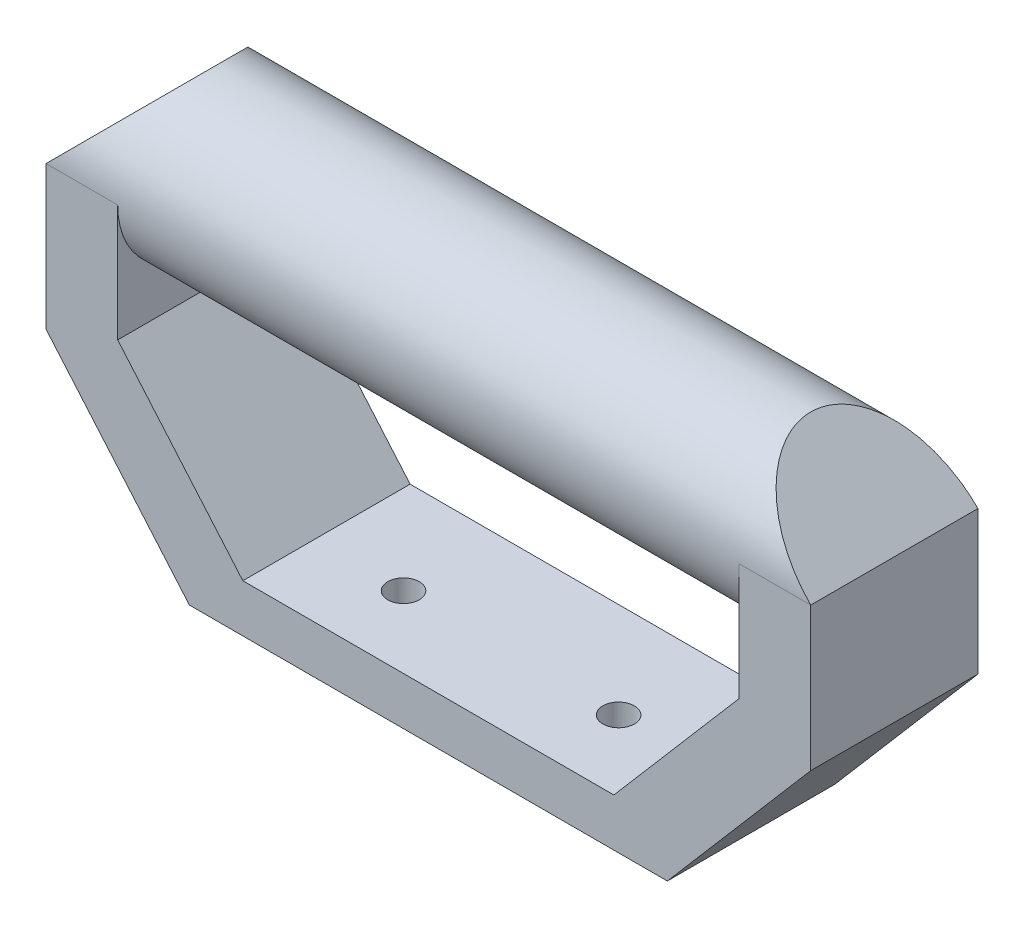
SolidWorks part; units mm, degrees
ref_plane "Front Plane" through (0, 0, 0) normal (0, 0, 1) x (1, 0, 0)
ref_plane "Top Plane" through (0, 0, 0) normal (0, 1, 0) x (1, 0, 0)
ref_plane "Right Plane" through (0, 0, 0) normal (1, 0, 0) x (0, 0, -1)
sketch "Sketch1" plane through (0, 0, 0) normal (0, 1, 0) x (1, 0, 0)
  line L1 (0, 0) -> (100, 0)
  line L2 (0, 0) -> (0, 35)
  line L3 (0, 35) -> (100, 35)
  line L4 (100, 0) -> (100, 35)
  dimension "D1" = 35
  dimension "D2" = 100
extrude "Boss-Extrude1" add sketch "Sketch1" along normal blind 10
sketch "Sketch2" plane through (0, 0, 0) normal (0, 0, 1) x (1, 0, 0)
  line L0 (0, 0) -> (-30, 35)
  line L1 (-30, 35) -> (-30, 65)
  line L2 (0, 0) -> (100, 0) construction
  line L3 (0, 10) -> (100, 10) construction
  line L4 (-30, 65) -> (-15, 65)
  line L5 (-15, 65) -> (-15, 40.5489)
  line L6 (-15, 40.5489) -> (11.1847, 10)
  line L7 (11.1847, 10) -> (0, 0)
  line L8 (50, 0) -> (50, 87.5) construction
  line L9 (115, 40.5489) -> (88.8153, 10)
  line L10 (115, 65) -> (115, 40.5489)
  line L11 (130, 65) -> (115, 65)
  line L12 (130, 35) -> (130, 65)
  line L13 (100, 0) -> (130, 35)
  line L14 (88.8153, 10) -> (100, 0)
  point P6 (50, 0)
  dimension "D1" = 80
  dimension "D2" = 25
  dimension "D3" = 30
  dimension "D4" = 15
  dimension "D5" = 15
extrude "Boss-Extrude2" add sketch "Sketch2" against normal up to surface (35 mm away) up to face at (50, 5, -35)
sketch "Sketch3" plane through (115, 0, 0) normal (-1, 0, 0) x (0, 0, 1)
  line L0 (-35, 65) -> (0, 65) construction
  circle A0 centre (-17.5, 65) radius 17.5
  dimension "D1" = 35
extrude "Boss-Extrude3" add sketch "Sketch3" along normal up to surface (130 mm away) up to face at (-15, 52.7744, -17.5)
chamfer "Chamfer1" distance 15 angle 45 2 edges at (-15, 65, -17.5) (115, 65, -17.5)
sketch "Sketch4" plane through (0, 0, -35) normal (0, 0, -1) x (-1, 0, 0)
  line L0 (-130, 65) -> (-112.5, 82.5)
  line L1 (15, 82.5) -> (-115, 82.5) construction
  line L2 (-112.5, 82.5) -> (-130, 82.5)
  line L3 (-130, 82.5) -> (-130, 65)
  line L4 (-50, 0) -> (-50, 82.5) construction
  line L5 (-100, 0) -> (0, 0) construction
  line L6 (12.5, 82.5) -> (30, 82.5)
  line L7 (30, 65) -> (12.5, 82.5)
  line L8 (30, 82.5) -> (30, 65)
extrude "Cut-Extrude1" cut sketch "Sketch4" against normal through all
sketch "Sketch5" plane through (0, 10, 0) normal (0, 1, 0) x (1, 0, 0)
  line L0 (88.8153, 15) -> (11.1847, 15) construction
  line L3 (88.8153, 35) -> (88.8153, 0) construction
  line L4 (11.1847, 35) -> (11.1847, 0) construction
  line L5 (50, 0) -> (50, 35) construction
  line L6 (11.1847, 0) -> (88.8153, 0) construction
  line L7 (88.8153, 35) -> (11.1847, 35) construction
  point P12 (74.8053, 15)
  point P13 (29.8053, 15)
  dimension "D1" = 20
  dimension "D2" = 45
  dimension "D3" = 14.01
  dimension "D4" = 18.6205
hole_wizard "M6 Clearance Hole1" positions "Sketch5" profile "Sketch6" hole size "M6" standard "ANSI Metric" end condition through all
sketch "Sketch6" plane through (29.8053, 10, -15) normal (1, 0, 0) x (0, 0, 1)
  line L0 (0, 0) -> (0, 10)
  line L1 (0, 10) -> (3.3, 10)
  line L2 (3.3, 10) -> (3.3, 0)
  line L5 (3.3, 0) -> (0, 0)
  line L11 (0, -6.35) -> (0, 107.95) construction
  dimension "Thru Hole Dia." = 6.6
  dimension "Thru Hole Depth" = 10
